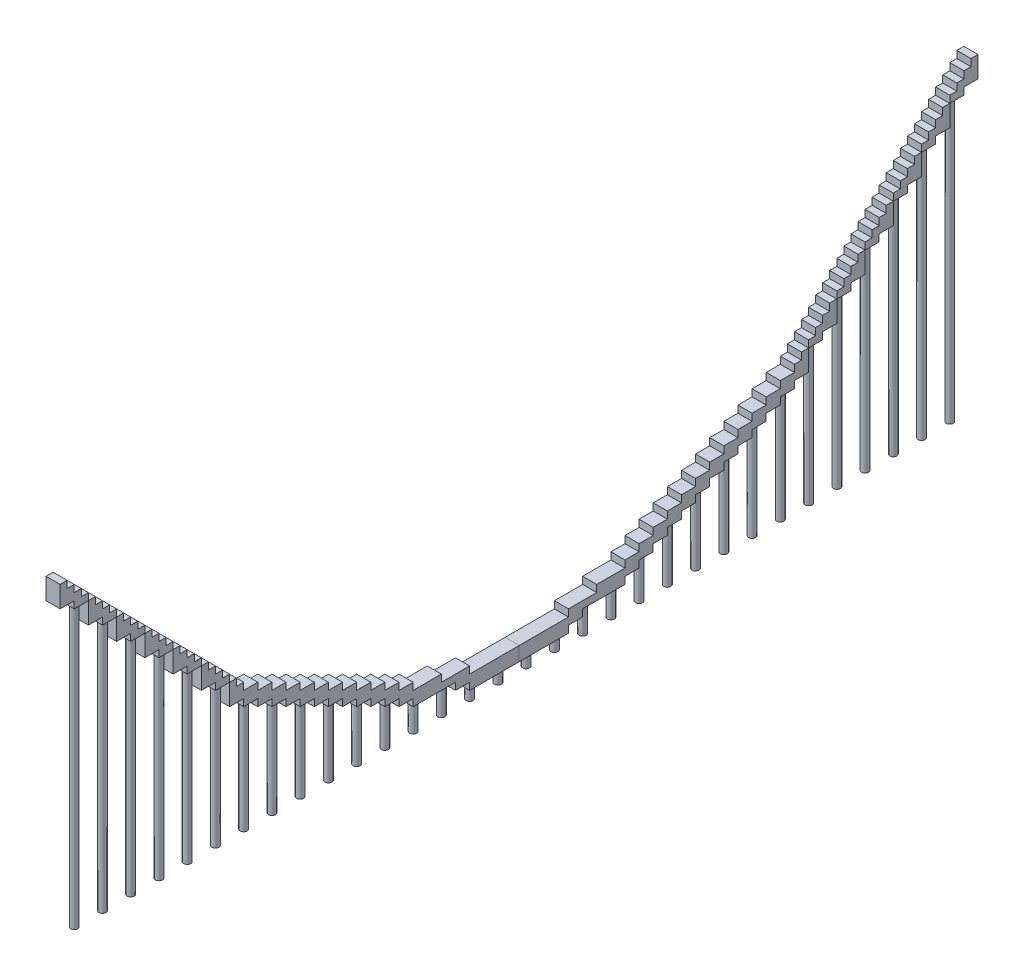
SolidWorks part; units mm, degrees
ref_plane "Ebene vorne" through (0, 0, 0) normal (0, 0, 1) x (1, 0, 0)
ref_plane "Ebene oben" through (0, 0, 0) normal (0, 1, 0) x (1, 0, 0)
ref_plane "Ebene rechts" through (0, 0, 0) normal (1, 0, 0) x (0, 0, -1)
sketch "Skizze1" plane through (0, 0, 0) normal (1, 0, 0) x (0, 0, -1)
  line L0 (-32.5, 0) -> (32.5, 0) construction
  line L1 (-32.5, 0) -> (-32.5, 22) construction
  line L2 (-32.5, 22) -> (32.5, 22) construction
  line L3 (32.5, 22) -> (32.5, 0) construction
  line L4 (0, 22) -> (0, 0) construction
  line L5 (-32.5, 22) -> (-10.5, 0) construction
  line L6 (-10.5, 0) -> (-32.5, 0) construction
  line L7 (0, 2) -> (-0.5, 2)
  line L8 (-0.5, 1) -> (0, 1)
  line L9 (0, 2) -> (0, 1)
  line L10 (-4.5, 2.5) -> (-5.5, 2.5)
  spline S0 degree 2 poles (-32.5, 22) (0, -18) (32.5, 22) knots 0 0 0 1 1 1 construction
  point P3 (0, 2)
  point P9 (-20.3125, 9.8125)
  line B0 (-31.5, 22) -> (-31.5, 21)
  line B1 (-32.5, 21) -> (-31.5, 21)
  line B2 (-32.5, 22) -> (-32.5, 21)
  line B3 (-32.5, 22) -> (-31.5, 22)
  line B4 (-30.5, 21) -> (-30.5, 20)
  line B5 (-31.5, 20) -> (-30.5, 20)
  line B6 (-31.5, 21) -> (-31.5, 20)
  line B7 (-31.5, 21) -> (-30.5, 21)
  line B8 (-29.5, 20) -> (-29.5, 19)
  line B9 (-30.5, 19) -> (-29.5, 19)
  line B10 (-30.5, 20) -> (-30.5, 19)
  line B11 (-30.5, 20) -> (-29.5, 20)
  line B12 (-28.5, 19) -> (-28.5, 18)
  line B13 (-29.5, 18) -> (-28.5, 18)
  line B14 (-29.5, 19) -> (-29.5, 18)
  line B15 (-29.5, 19) -> (-28.5, 19)
  line B16 (-27.5, 18) -> (-27.5, 17)
  line B17 (-28.5, 17) -> (-27.5, 17)
  line B18 (-28.5, 18) -> (-28.5, 17)
  line B19 (-28.5, 18) -> (-27.5, 18)
  line B20 (-26.5, 17) -> (-26.5, 16)
  line B21 (-27.5, 16) -> (-26.5, 16)
  line B22 (-27.5, 17) -> (-27.5, 16)
  line B23 (-27.5, 17) -> (-26.5, 17)
  line B24 (-25.5, 16) -> (-25.5, 15)
  line B25 (-26.5, 15) -> (-25.5, 15)
  line B26 (-26.5, 16) -> (-26.5, 15)
  line B27 (-26.5, 16) -> (-25.5, 16)
  line B28 (-24.5, 15) -> (-24.5, 14)
  line B29 (-25.5, 14) -> (-24.5, 14)
  line B30 (-25.5, 15) -> (-25.5, 14)
  line B31 (-25.5, 15) -> (-24.5, 15)
  line B32 (-23.5, 14) -> (-23.5, 13)
  line B33 (-24.5, 13) -> (-23.5, 13)
  line B34 (-24.5, 14) -> (-24.5, 13)
  line B35 (-24.5, 14) -> (-23.5, 14)
  line B36 (-22.5, 13) -> (-22.5, 12)
  line B37 (-23.5, 12) -> (-22.5, 12)
  line B38 (-23.5, 13) -> (-23.5, 12)
  line B39 (-23.5, 13) -> (-22.5, 13)
  line B40 (-21.5, 12) -> (-21.5, 11)
  line B41 (-22.5, 11) -> (-21.5, 11)
  line B42 (-22.5, 12) -> (-22.5, 11)
  line B43 (-22.5, 12) -> (-21.5, 12)
  line B44 (-20.5, 11) -> (-20.5, 10)
  line B45 (-21.5, 10) -> (-20.5, 10)
  line B46 (-21.5, 11) -> (-21.5, 10)
  line B47 (-21.5, 11) -> (-20.5, 11)
  line B48 (-19.5, 10) -> (-19.5, 9)
  line B49 (-20.5, 9) -> (-19.5, 9)
  line B50 (-20.5, 10) -> (-20.5, 9)
  line B51 (-20.5, 10) -> (-19.5, 10)
  line B52 (-18.5, 9) -> (-18.5, 8)
  line B53 (-19.5, 8) -> (-18.5, 8)
  line B54 (-19.5, 9) -> (-19.5, 8)
  line B55 (-19.5, 9) -> (-18.5, 9)
  line B56 (-17.5, 8.5) -> (-17.5, 7.5)
  line B57 (-18.5, 7.5) -> (-17.5, 7.5)
  line B58 (-18.5, 8.5) -> (-18.5, 7.5)
  line B59 (-18.5, 8.5) -> (-17.5, 8.5)
  line B60 (-16.5, 8) -> (-16.5, 7)
  line B61 (-17.5, 7) -> (-16.5, 7)
  line B62 (-17.5, 8) -> (-17.5, 7)
  line B63 (-17.5, 8) -> (-16.5, 8)
  line B64 (-15.5, 7.5) -> (-15.5, 6.5)
  line B65 (-16.5, 6.5) -> (-15.5, 6.5)
  line B66 (-16.5, 7.5) -> (-16.5, 6.5)
  line B67 (-16.5, 7.5) -> (-15.5, 7.5)
  line B68 (-14.5, 7) -> (-14.5, 6)
  line B69 (-15.5, 6) -> (-14.5, 6)
  line B70 (-15.5, 7) -> (-15.5, 6)
  line B71 (-15.5, 7) -> (-14.5, 7)
  line B72 (-13.5, 6.5) -> (-13.5, 5.5)
  line B73 (-14.5, 5.5) -> (-13.5, 5.5)
  line B74 (-14.5, 6.5) -> (-14.5, 5.5)
  line B75 (-14.5, 6.5) -> (-13.5, 6.5)
  line B76 (-12.5, 6) -> (-12.5, 5)
  line B77 (-13.5, 5) -> (-12.5, 5)
  line B78 (-13.5, 6) -> (-13.5, 5)
  line B79 (-13.5, 6) -> (-12.5, 6)
  line B80 (-11.5, 5.5) -> (-11.5, 4.5)
  line B81 (-12.5, 4.5) -> (-11.5, 4.5)
  line B82 (-12.5, 5.5) -> (-12.5, 4.5)
  line B83 (-12.5, 5.5) -> (-11.5, 5.5)
  line B84 (-10.5, 5) -> (-10.5, 4)
  line B85 (-11.5, 4) -> (-10.5, 4)
  line B86 (-11.5, 5) -> (-11.5, 4)
  line B87 (-11.5, 5) -> (-10.5, 5)
  line B88 (-9.5, 4.5) -> (-9.5, 3.5)
  line B89 (-10.5, 3.5) -> (-9.5, 3.5)
  line B90 (-10.5, 4.5) -> (-10.5, 3.5)
  line B91 (-10.5, 4.5) -> (-9.5, 4.5)
  line B92 (-8.5, 4) -> (-8.5, 3)
  line B93 (-9.5, 3) -> (-8.5, 3)
  line B94 (-9.5, 4) -> (-9.5, 3)
  line B95 (-9.5, 4) -> (-8.5, 4)
  line B96 (-7.5, 3.5) -> (-7.5, 2.5)
  line B97 (-8.5, 2.5) -> (-7.5, 2.5)
  line B98 (-8.5, 3.5) -> (-8.5, 2.5)
  line B99 (-8.5, 3.5) -> (-7.5, 3.5)
  line B100 (-6.5, 3) -> (-6.5, 2)
  line B101 (-7.5, 2) -> (-6.5, 2)
  line B102 (-7.5, 3) -> (-7.5, 2)
  line B103 (-7.5, 3) -> (-6.5, 3)
  line B104 (-5.5, 3) -> (-5.5, 2)
  line B105 (-6.5, 2) -> (-5.5, 2)
  line B106 (-6.5, 3) -> (-6.5, 2)
  line B107 (-6.5, 3) -> (-5.5, 3)
  line B108 (-4.5, 3) -> (-4.5, 2)
  line B109 (-5.5, 2) -> (-4.5, 2)
  line B110 (-5.5, 3) -> (-5.5, 2)
  line B111 (-5.5, 3) -> (-4.5, 3)
  line B112 (-3.5, 2.5) -> (-3.5, 1.5)
  line B113 (-4.5, 1.5) -> (-3.5, 1.5)
  line B114 (-4.5, 2.5) -> (-4.5, 1.5)
  line B115 (-4.5, 2.5) -> (-3.5, 2.5)
  line B116 (-2.5, 2) -> (-2.5, 1)
  line B117 (-3.5, 1) -> (-2.5, 1)
  line B118 (-3.5, 2) -> (-3.5, 1)
  line B119 (-3.5, 2) -> (-2.5, 2)
  line B120 (-1.5, 2) -> (-1.5, 1)
  line B121 (-2.5, 1) -> (-1.5, 1)
  line B122 (-2.5, 2) -> (-2.5, 1)
  line B123 (-2.5, 2) -> (-1.5, 2)
  line B124 (-0.5, 2) -> (-0.5, 1)
  line B125 (-1.5, 1) -> (-0.5, 1)
  line B126 (-1.5, 2) -> (-1.5, 1)
  line B127 (-1.5, 2) -> (-0.5, 2)
  dimension "D1" = 65
  dimension "D2" = 22
  dimension "D3" = 2
  dimension "D4" = 12.1875
sketch_block_instance "Block1-1"
sketch_block "Block1"
sketch_block_instance "Block1-2"
sketch_block_instance "Block1-3"
sketch_block_instance "Block1-4"
sketch_block_instance "Block1-5"
sketch_block_instance "Block1-6"
sketch_block_instance "Block1-7"
sketch_block_instance "Block1-8"
sketch_block_instance "Block1-9"
sketch_block_instance "Block1-10"
sketch_block_instance "Block1-11"
sketch_block_instance "Block1-12"
sketch_block_instance "Block1-13"
sketch_block_instance "Block1-14"
sketch_block_instance "Block1-15"
sketch_block_instance "Block1-16"
sketch_block_instance "Block1-17"
sketch_block_instance "Block1-18"
sketch_block_instance "Block1-19"
sketch_block_instance "Block1-20"
sketch_block_instance "Block1-21"
sketch_block_instance "Block1-22"
sketch_block_instance "Block1-23"
sketch_block_instance "Block1-24"
sketch_block_instance "Block1-25"
sketch_block_instance "Block1-26"
sketch_block_instance "Block1-27"
sketch_block_instance "Block1-28"
sketch_block_instance "Block1-29"
sketch_block_instance "Block1-30"
sketch_block_instance "Block1-31"
sketch_block_instance "Block1-32"
extrude "Aufsatz-Linear austragen1" add sketch "Skizze1" along normal mid plane 1 contours B55 B54 B53 B52 | B3 B2 B1 B0 | B7 B6 B5 B4 | B11 B10 B9 B8 | B15 B14 B13 B12 | B19 B18 B17 B16 | B23 B22 B21 B20 | B27 B26 B25 B24 | B31 B30 B29 B28 | B35 B34 B33 B32 | B39 B38 B37 B36 | B43 B42 B41 B40 | B47 B46 B45 B44 | B51 B50 B49 B48 | B59 B52 B58 B57 B56 | B63 B56 B62 B61 B60 | B67 B60 B66 B65 B64 | B71 B64 B70 B69 B68 | B75 B68 B74 B73 B72 | B79 B72 B78 B77 B76 | B83 B76 B82 B81 B80 | B87 B80 B86 B85 B84 | B91 B84 B90 B89 B88 | B95 B88 B94 B93 B92 | B99 B92 B98 B97 B96 | B103 B96 B102 B101 B100 | B107 B100 B105 B104 | B115 B108 B114 B113 B112 | B119 B112 B118 B117 B116 | B123 B116 B121 B120 | B127 B120 B125 B124 | L7 B124 L8 L9 | B104 B109 B108 L10 region at (0, 1.5, 0.25) region at (0, 21.5, 32) region at (0, 20.5, 31) region at (0, 19.5, 30) region at (0, 18.5, 29) region at (0, 17.5, 28) region at (0, 16.5, 27) region at (0, 15.5, 26) region at (0, 14.5, 25) region at (0, 13.5, 24) region at (0, 12.5, 23) region at (0, 11.5, 22) region at (0, 10.5, 21) region at (0, 9.5, 20) region at (0, 1.5, 1) region at (0, 1.5, 2) region at (0, 1.5, 3) region at (0, 2, 4) region at (0, 2.25, 5) region at (0, 2.5, 6) region at (0, 2.5, 7) region at (0, 3, 8) region at (0, 3.5, 9) region at (0, 4, 10) region at (0, 4.5, 11) region at (0, 5, 12) region at (0, 5.5, 13) region at (0, 6, 14) region at (0, 6.5, 15) region at (0, 7, 16) region at (0, 7.5, 17) region at (0, 8, 18) region at (0, 8.5, 19)
sketch "Skizze2" plane through (0.5, 0, 0) normal (1, 0, 0) x (0, 0, -1)
  line L0 (-32.5, 22) -> (-32.5, 21) construction
  line L1 (-32.5, 21) -> (-31.5, 21)
  line L2 (-32.5, 21) -> (-32.5, 20.5)
  line L3 (-32.5, 20.5) -> (-31.5, 20.5)
  line L4 (-31.5, 21) -> (-31.5, 20.5)
  line L5 (-32.5, 21) -> (-31.5, 21) construction
  line L6 (-31.5, 21) -> (-31.5, 20) construction
  line L7 (-30.5, 21) -> (-30.5, 20) construction
  line L8 (-30.5, 20.5) -> (-29.5, 20.5)
  line L9 (-30.5, 20.5) -> (-30.5, 20)
  line L10 (-30.5, 20) -> (-29.5, 20)
  line L11 (-29.5, 20.5) -> (-29.5, 20)
  line L12 (-30.5, 20) -> (-29.5, 20) construction
  line L13 (-29.5, 19) -> (-29.5, 18) construction
  line L14 (-30.5, 19) -> (-29.5, 19)
  line L15 (-30.5, 19) -> (-30.5, 18.5)
  line L16 (-30.5, 18.5) -> (-29.5, 18.5)
  line L17 (-29.5, 19) -> (-29.5, 18.5)
  line L18 (-28.5, 19) -> (-28.5, 18) construction
  line L19 (-28.5, 18.5) -> (-27.5, 18.5)
  line L20 (-28.5, 18.5) -> (-28.5, 18)
  line L21 (-28.5, 18) -> (-27.5, 18)
  line L22 (-27.5, 18.5) -> (-27.5, 18)
  line L23 (-27.5, 17) -> (-27.5, 16) construction
  line L24 (-28.5, 17) -> (-27.5, 17)
  line L25 (-28.5, 17) -> (-28.5, 16.5)
  line L26 (-28.5, 16.5) -> (-27.5, 16.5)
  line L27 (-27.5, 17) -> (-27.5, 16.5)
  line L28 (-26.5, 17) -> (-26.5, 16) construction
  line L29 (-26.5, 16.5) -> (-25.5, 16.5)
  line L30 (-26.5, 16.5) -> (-26.5, 16)
  line L31 (-26.5, 16) -> (-25.5, 16)
  line L32 (-25.5, 16.5) -> (-25.5, 16)
  line L33 (-25.5, 15) -> (-25.5, 14) construction
  line L34 (-26.5, 15) -> (-25.5, 15)
  line L35 (-26.5, 15) -> (-26.5, 14.5)
  line L36 (-26.5, 14.5) -> (-25.5, 14.5)
  line L37 (-25.5, 15) -> (-25.5, 14.5)
  line L38 (-24.5, 15) -> (-24.5, 14) construction
  line L39 (-24.5, 14.5) -> (-23.5, 14.5)
  line L40 (-24.5, 14.5) -> (-24.5, 14)
  line L41 (-24.5, 14) -> (-23.5, 14)
  line L42 (-23.5, 14.5) -> (-23.5, 14)
  line L43 (-23.5, 13) -> (-23.5, 12) construction
  line L44 (-24.5, 13) -> (-23.5, 13)
  line L45 (-24.5, 13) -> (-24.5, 12.5)
  line L46 (-24.5, 12.5) -> (-23.5, 12.5)
  line L47 (-23.5, 13) -> (-23.5, 12.5)
  line L48 (-22.5, 13) -> (-22.5, 12) construction
  line L49 (-22.5, 12.5) -> (-21.5, 12.5)
  line L50 (-22.5, 12.5) -> (-22.5, 12)
  line L51 (-22.5, 12) -> (-21.5, 12)
  line L52 (-21.5, 12.5) -> (-21.5, 12)
  line L53 (-21.5, 11) -> (-21.5, 10) construction
  line L54 (-22.5, 11) -> (-21.5, 11)
  line L55 (-22.5, 11) -> (-22.5, 10.5)
  line L56 (-22.5, 10.5) -> (-21.5, 10.5)
  line L57 (-21.5, 11) -> (-21.5, 10.5)
  line L58 (-20.5, 11) -> (-20.5, 10) construction
  line L59 (-20.5, 10.5) -> (-19.5, 10.5)
  line L60 (-20.5, 10.5) -> (-20.5, 10)
  line L61 (-20.5, 10) -> (-19.5, 10)
  line L62 (-19.5, 10.5) -> (-19.5, 10)
  line L64 (-19.5, 9) -> (-19.5, 8) construction
  line L69 (-20.5, 8.5) -> (-19.5, 8.5)
  line L70 (-20.5, 8.5) -> (-20.5, 9)
  line L71 (-20.5, 9) -> (-19.5, 9)
  line L72 (-19.5, 8.5) -> (-19.5, 9)
  line L73 (-29.5, 20) -> (-29.5, 19) construction
extrude "Aufsatz-Linear austragen2" add sketch "Skizze2" against normal blind 1 contours L4 L1 L2 L3 | L17 L14 L15 L16 | L27 L24 L25 L26 | L37 L34 L35 L36 | L47 L44 L45 L46 | L57 L54 L55 L56 | L71 L72 L69 L70 region at (0.5, 20.75, 32) region at (0.5, 18.75, 30) region at (0.5, 16.75, 28) region at (0.5, 14.75, 26) region at (0.5, 12.75, 24) region at (0.5, 10.75, 22)
sketch "Skizze4" plane through (0, 0, 0) normal (0, 1, 0) x (1, 0, 0)
  line L0 (0, -32.5) -> (0, -31) construction
  line L1 (-0.5, -32.5) -> (0.5, -32.5) construction
  line L2 (0, -31) -> (0, -29) construction
  line L3 (0, -29) -> (0, -27) construction
  line L4 (0, -27) -> (0, -25) construction
  line L5 (0, -25) -> (0, -23) construction
  line L6 (0, -23) -> (0, -21) construction
  line L7 (0, -21) -> (0, -19) construction
  line L8 (0, -19) -> (0, -17) construction
  line L9 (0, -17) -> (0, -15) construction
  line L10 (0, -15) -> (0, -13) construction
  line L11 (0, -13) -> (0, -11) construction
  line L12 (0, -11) -> (0, -9) construction
  line L13 (0, -9) -> (0, -7) construction
  line L14 (0, -7) -> (0, -5) construction
  line L15 (0, -5) -> (0, -3) construction
  line L16 (0, -3) -> (0, -1) construction
  circle A0 centre (0, -31) radius 0.25
  circle A1 centre (0, -29) radius 0.25
  circle A2 centre (0, -27) radius 0.25
  circle A3 centre (0, -25) radius 0.25
  circle A4 centre (0, -23) radius 0.25
  circle A5 centre (0, -21) radius 0.25
  circle A6 centre (0, -19) radius 0.25
  circle A7 centre (0, -17) radius 0.25
  circle A8 centre (0, -15) radius 0.25
  circle A9 centre (0, -13) radius 0.25
  circle A10 centre (0, -11) radius 0.25
  circle A11 centre (0, -9) radius 0.25
  circle A12 centre (0, -7) radius 0.25
  circle A13 centre (0, -5) radius 0.25
  circle A14 centre (0, -3) radius 0.25
  circle A15 centre (0, -1) radius 0.25
  dimension "D1" = 1.5
  dimension "D3" = 0.5
  dimension "D2" = 2
extrude "Aufsatz-Linear austragen3" add sketch "Skizze4" along normal up to next
sketch "Skizze5" plane through (0.5, 0, 0) normal (1, 0, 0) x (0, 0, -1)
  line L0 (-32.5, 22) -> (-31.5, 22) construction
  line L1 (-32, 22) -> (-31.5, 22)
  line L2 (-32, 22) -> (-32, 21.5)
  line L3 (-32, 21.5) -> (-31.5, 21.5)
  line L4 (-31.5, 22) -> (-31.5, 21.5)
  line L5 (-31.5, 22) -> (-31.5, 21) construction
  line L6 (-31.5, 21) -> (-30.5, 21) construction
  line L7 (-31, 21) -> (-30.5, 21)
  line L8 (-31, 21) -> (-31, 20.5)
  line L9 (-31, 20.5) -> (-30.5, 20.5)
  line L10 (-30.5, 21) -> (-30.5, 20.5)
  line L11 (-30.5, 21) -> (-30.5, 20) construction
  line L12 (-30.5, 20) -> (-29.5, 20) construction
  line L13 (-30, 20) -> (-29.5, 20)
  line L14 (-30, 20) -> (-30, 19.5)
  line L15 (-30, 19.5) -> (-29.5, 19.5)
  line L16 (-29.5, 20) -> (-29.5, 19.5)
  line L17 (-29.5, 20) -> (-29.5, 19) construction
  line L18 (-29.5, 19) -> (-28.5, 19) construction
  line L19 (-29, 19) -> (-28.5, 19)
  line L20 (-29, 19) -> (-29, 18.5)
  line L21 (-29, 18.5) -> (-28.5, 18.5)
  line L22 (-28.5, 19) -> (-28.5, 18.5)
  line L23 (-28.5, 19) -> (-28.5, 18) construction
  line L24 (-28.5, 18) -> (-27.5, 18) construction
  line L25 (-28, 18) -> (-27.5, 18)
  line L26 (-28, 18) -> (-28, 17.5)
  line L27 (-28, 17.5) -> (-27.5, 17.5)
  line L28 (-27.5, 18) -> (-27.5, 17.5)
  line L29 (-27.5, 18) -> (-27.5, 17) construction
  line L30 (-27.5, 17) -> (-26.5, 17) construction
  line L31 (-27, 17) -> (-26.5, 17)
  line L32 (-27, 17) -> (-27, 16.5)
  line L33 (-27, 16.5) -> (-26.5, 16.5)
  line L34 (-26.5, 17) -> (-26.5, 16.5)
  line L35 (-26.5, 17) -> (-26.5, 16) construction
  line L36 (-26.5, 16) -> (-25.5, 16) construction
  line L37 (-26, 16) -> (-25.5, 16)
  line L38 (-26, 16) -> (-26, 15.5)
  line L39 (-26, 15.5) -> (-25.5, 15.5)
  line L40 (-25.5, 16) -> (-25.5, 15.5)
  line L41 (-25.5, 16) -> (-25.5, 15) construction
  line L42 (-25.5, 15) -> (-24.5, 15) construction
  line L43 (-25, 15) -> (-24.5, 15)
  line L44 (-25, 15) -> (-25, 14.5)
  line L45 (-25, 14.5) -> (-24.5, 14.5)
  line L46 (-24.5, 15) -> (-24.5, 14.5)
  line L47 (-24.5, 15) -> (-24.5, 14) construction
  line L48 (-24.5, 14) -> (-23.5, 14) construction
  line L49 (-24, 14) -> (-23.5, 14)
  line L50 (-24, 14) -> (-24, 13.5)
  line L51 (-24, 13.5) -> (-23.5, 13.5)
  line L52 (-23.5, 14) -> (-23.5, 13.5)
  line L53 (-23.5, 14) -> (-23.5, 13) construction
  line L54 (-23.5, 13) -> (-22.5, 13) construction
  line L55 (-23, 13) -> (-22.5, 13)
  line L56 (-23, 13) -> (-23, 12.5)
  line L57 (-23, 12.5) -> (-22.5, 12.5)
  line L58 (-22.5, 13) -> (-22.5, 12.5)
  line L59 (-22.5, 13) -> (-22.5, 12) construction
  line L60 (-22.5, 12) -> (-21.5, 12) construction
  line L61 (-22, 12) -> (-21.5, 12)
  line L62 (-22, 12) -> (-22, 11.5)
  line L63 (-22, 11.5) -> (-21.5, 11.5)
  line L64 (-21.5, 12) -> (-21.5, 11.5)
  line L65 (-21.5, 12) -> (-21.5, 11) construction
  line L66 (-21.5, 11) -> (-20.5, 11) construction
  line L67 (-21, 11) -> (-20.5, 11)
  line L68 (-21, 11) -> (-21, 10.5)
  line L69 (-21, 10.5) -> (-20.5, 10.5)
  line L70 (-20.5, 11) -> (-20.5, 10.5)
  line L71 (-20.5, 11) -> (-20.5, 10) construction
  line L73 (-20.5, 10) -> (-19.5, 10) construction
  line L74 (-20, 10) -> (-19.5, 10)
  line L75 (-20, 10) -> (-20, 9.5)
  line L76 (-20, 9.5) -> (-19.5, 9.5)
  line L79 (-19.5, 10) -> (-19.5, 9.5)
  line L80 (-19.5, 10) -> (-19.5, 9) construction
extrude "Schnitt-Linear austragen1" cut sketch "Skizze5" against normal through all
mirror "Spiegeln1" about plane through (0.5, 0, 0) normal (0, 0, -1) of bodies 154 149 148 147 146 145 144 114 113 112 111 110 109 108 107 106 105 104 103 102 101
